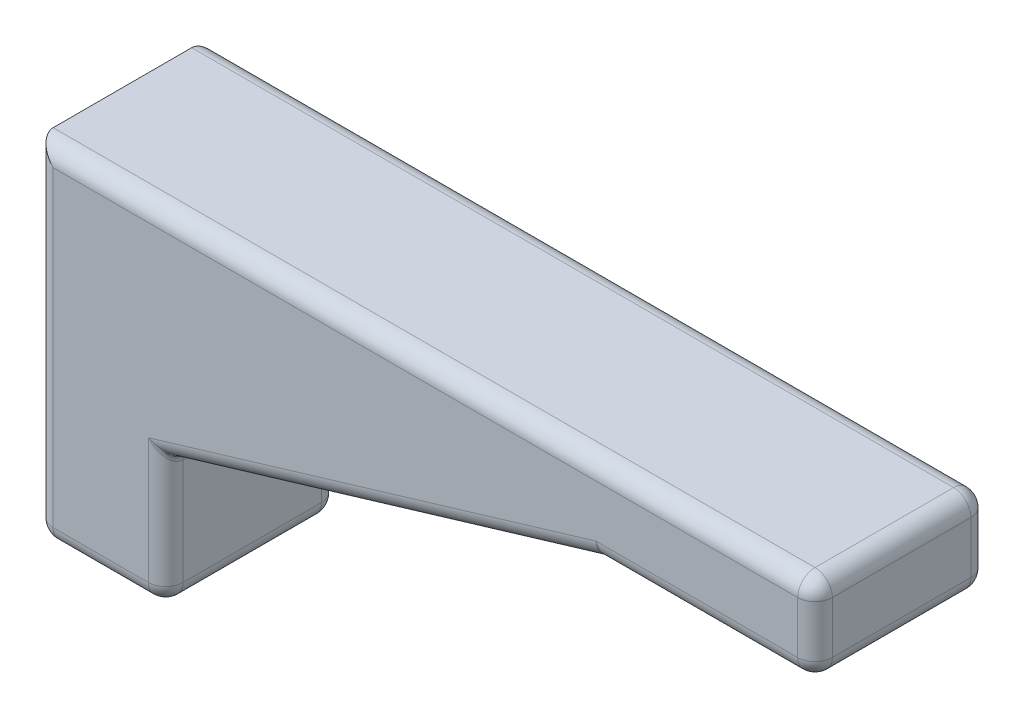
SolidWorks part; units mm, degrees
material "PLA"
ref_plane "Alzado" through (0, 0, 0) normal (0, 0, 1) x (1, 0, 0)
ref_plane "Planta" through (0, 0, 0) normal (0, 1, 0) x (1, 0, 0)
ref_plane "Vista lateral" through (0, 0, 0) normal (1, 0, 0) x (0, 0, -1)
sketch "Croquis1" plane through (0, 0, 0) normal (0, 0, 1) x (1, 0, 0)
  line L0 (0, 0) -> (0, 40)
  line L1 (0, 40) -> (90, 40)
  line L2 (90, 40) -> (90, 30)
  line L3 (90, 30) -> (15, 30)
  line L4 (15, 30) -> (15, 0)
  line L5 (15, 0) -> (0, 0)
  dimension "D1" = 90
  dimension "D2" = 40
  dimension "D3" = 10
  dimension "D4" = 15
extrude "Saliente-Extruir1" add sketch "Croquis1" along normal blind 20
sketch "Croquis2" plane through (15, 0, 0) normal (1, 0, 0) x (0, 0, -1)
  line L0 (-10, 0) -> (-10, 40) construction
  line L1 (-20, 0) -> (0, 0) construction
  line L2 (-20, 40) -> (0, 40) construction
  circle A0 centre (-10, 20) radius 2.625
  circle A1 centre (-10, 10) radius 2.625
  dimension "D1" = 5.25
  dimension "D2" = 5.25
  dimension "D3" = 10
  dimension "D4" = 10
extrude "Cortar-Extruir1" cut sketch "Croquis2" against normal blind 30
sketch "Croquis3" plane through (15, 0, 0) normal (1, 0, 0) x (0, 0, -1)
  circle A0 centre (-10, 20) radius 4.75
  circle A1 centre (-10, 10) radius 4.75
  dimension "D1" = 9.5
  dimension "D2" = 9.5
extrude "Cortar-Extruir2" cut sketch "Croquis3" against normal blind 6
sketch "Croquis6" plane through (0, 0, 20) normal (0, 0, 1) x (1, 0, 0)
  line L0 (15, 30) -> (65, 30)
  line L1 (15, 30) -> (90, 30) construction
  line L2 (65, 30) -> (15, 15)
  line L3 (15, 15) -> (15, 30)
  dimension "D1" = 15
  dimension "D2" = 50
extrude "Saliente-Extruir2" add sketch "Croquis6" against normal blind 5
sketch "Croquis7" plane through (0, 0, 0) normal (0, 0, -1) x (-1, 0, 0)
  line L0 (-15, 30) -> (-65, 30)
  line L1 (-15, 30) -> (-90, 30) construction
  line L2 (-15, 15) -> (-65, 30) construction
  line L3 (-65, 30) -> (-15, 15)
  line L4 (-15, 0) -> (-15, 30) construction
  line L5 (-15, 15) -> (-15, 30)
  dimension "D1" = 50
extrude "Saliente-Extruir3" add sketch "Croquis7" against normal blind 5
fillet "Redondeo5" radius 2 18 edges at (0, 0, 10) (15, 0, 10) (90, 30, 10) (90, 40, 10) (15, 7.5, 0) (40, 22.5, 0) (77.5, 30, 0) (90, 35, 0) (45, 40, 0) (0, 20, 0) (7.5, 0, 0) (7.5, 0, 20) (0, 20, 20) (45, 40, 20) (90, 35, 20) (77.5, 30, 20) (40, 22.5, 20) (15, 7.5, 20)
fillet "Redondeo6" radius 3 1 edges at (15, 30, 10)
fillet "Redondeo7" radius 1 2 edges at (40, 22.5, 5) (40, 22.5, 15)
fillet "Redondeo8" radius 1 18 edges at (64.914, 30.5858, 19.4142) (65, 30, 17) (63.9807, 30, 15.2929) (14.4142, 15.4358, 19.4142) (15, 15, 17) (15, 15.3058, 15.2929) (15, 21.522, 15) (15.8787, 29.1213, 15) (14.4142, 15.4358, 0.5858) (15, 15, 3) (15, 15.3058, 4.7071) (15, 21.522, 5) (15.8787, 29.1213, 5) (64.914, 30.5858, 0.5858) (65, 30, 3) (63.9807, 30, 4.7071) (39.7599, 30, 15) (39.7599, 30, 5)
sketch "Croquis8" plane through (15, 0, 0) normal (1, 0, 0) x (0, 0, -1)
  circle A0 centre (-10, 10) radius 4.75
extrude "Saliente-Extruir4" add sketch "Croquis8" against normal through all
